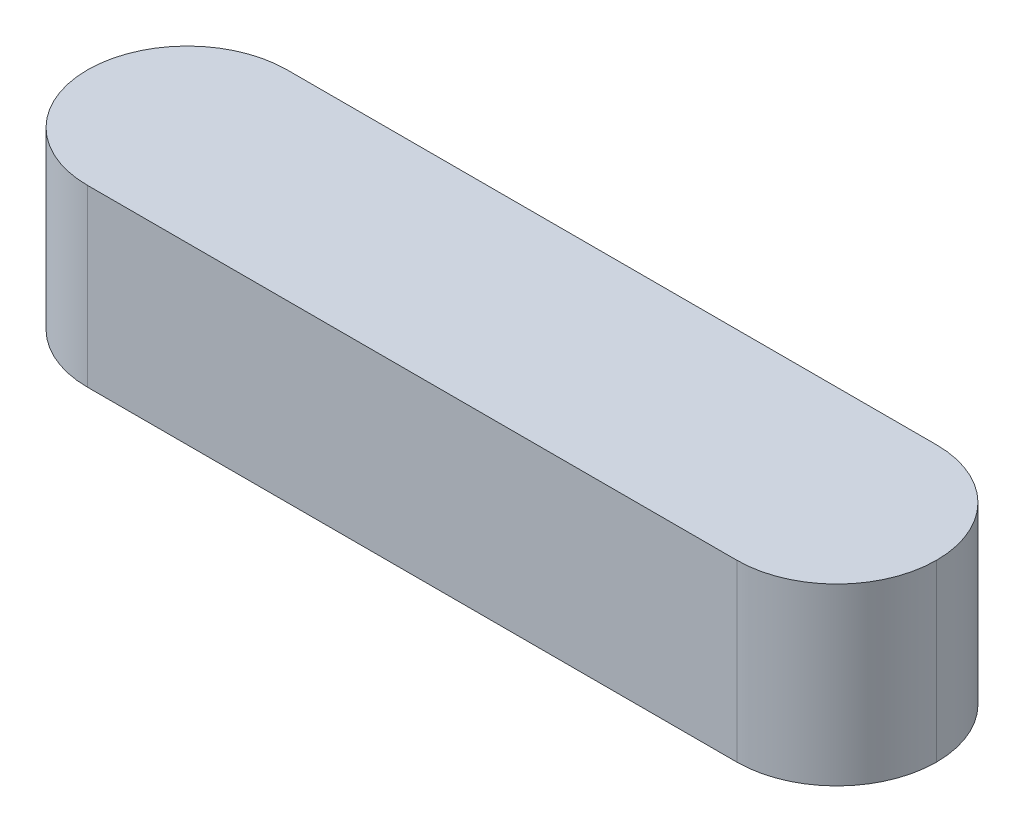
SolidWorks part; units mm, degrees
ref_plane "Front Plane" through (0, 0, 0) normal (0, 0, 1) x (1, 0, 0)
ref_plane "Top Plane" through (0, 0, 0) normal (0, 1, 0) x (1, 0, 0)
ref_plane "Right Plane" through (0, 0, 0) normal (1, 0, 0) x (0, 0, -1)
sketch "Sketch1" plane through (0, 0, 0) normal (0, 1, 0) x (1, 0, 0)
  line L1 (-9.9098, 8) -> (24.0902, 8)
  line L2 (-9.9098, 8) -> (-9.9098, 0)
  line L3 (-9.9098, 0) -> (24.0902, 0)
  line L4 (24.0902, 8) -> (24.0902, 0)
  dimension "D1" = 34
  dimension "D2" = 8
extrude "Boss-Extrude1" add sketch "Sketch1" along normal blind 7
fillet "Fillet1" radius 4 4 edges at (24.0902, 3.5, -8) (24.0902, 3.5, 0) (-9.9098, 3.5, -8) (-9.9098, 3.5, 0)
